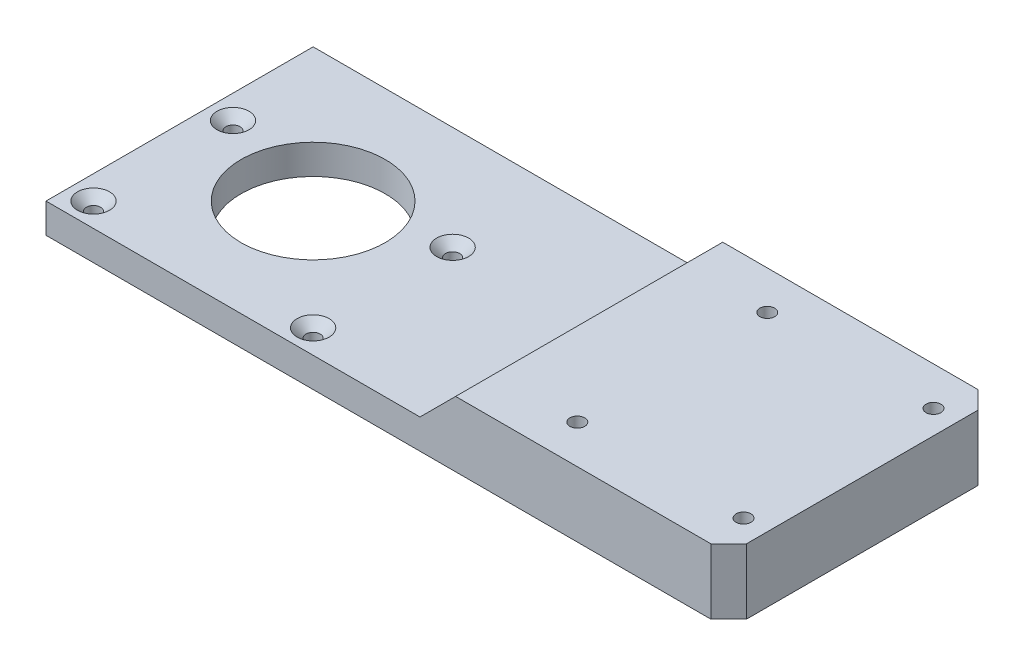
SolidWorks part; units mm, degrees
material "7075-T6, Plate (SS)"
ref_plane "Front Plane" through (0, 0, 0) normal (0, 0, 1) x (1, 0, 0)
ref_plane "Top Plane" through (0, 0, 0) normal (0, 1, 0) x (1, 0, 0)
ref_plane "Right Plane" through (0, 0, 0) normal (1, 0, 0) x (0, 0, -1)
sketch "Sketch1" plane through (0, 0, 0) normal (0, 1, 0) x (1, 0, 0)
  line L1 (0, -22.5) -> (115, -22.5)
  line L2 (0, -22.5) -> (0, 22.5)
  line L3 (0, 22.5) -> (115, 22.5)
  line L4 (115, -22.5) -> (115, 22.5)
  dimension "D1" = 45
  dimension "D2" = 115
extrude "Boss-Extrude1" add sketch "Sketch1" along normal blind 5 contours L2 L3 L4 L1
sketch "Sketch2" plane through (0, 5, 0) normal (0, 1, 0) x (1, 0, 0)
  line L0 (0, -22.5) -> (0, 22.5) construction
  circle A0 centre (22.5, 0) radius 12.142
  dimension "D2" = 24.284
  dimension "D1" = 22.5
extrude "Cut-Extrude1" cut sketch "Sketch2" against normal up to next
cosmetic thread "Cosmetic Thread1" parameters "D2"=25
hole_wizard "CSK for M2 Countersunk Flat Head Screw1" positions "Sketch3" profile "Sketch4" countersink size "M2" standard "DIN" end condition through all
sketch "Sketch3" plane through (0, 5, 0) normal (0, 1, 0) x (1, 0, 0)
  line L2 (0, -22.5) -> (115, -22.5) construction
  point P6 (4, -18.5)
  point P48 (41, -18.5)
  point P50 (41, 5)
  point P52 (4, 5)
  dimension "D3" = 4
  dimension "D5" = 37
  dimension "D6" = 27.5
sketch "Sketch4" plane through (4, 5, 18.5) normal (1, 0, 0) x (0, 0, 1)
  line L0 (0, 0) -> (0, 5)
  line L1 (0, 5) -> (1.2, 5)
  line L2 (1.2, 5) -> (1.2, 1.5)
  line L3 (1.2, 1.5) -> (2.7, 0)
  line L5 (2.7, 0) -> (0, 0)
  line L6 (-1.2, 1.5) -> (-2.7, 0) construction
  line L11 (0, -6.35) -> (0, 107.95) construction
  dimension "Thru Hole Dia." = 2.4
  dimension "Thru Hole Depth" = 5
  dimension "Near C'Sink Dia." = 5.4
  dimension "Near C'Sink Angle" = 90
sketch "Sketch13" plane through (0, 5, 0) normal (0, 1, 0) x (1, 0, 0)
  line L0 (0, -22.5) -> (115, -22.5) construction
  line L1 (115, 22.5) -> (63, 22.5)
  line L2 (115, 22.5) -> (115, -22.5)
  line L3 (115, -22.5) -> (63, -22.5)
  line L4 (63, 22.5) -> (63, -22.5)
  dimension "D1" = 52
extrude "Boss-Extrude4" add sketch "Sketch13" along normal blind 6
chamfer "Chamfer2" distance 6 angle 45 1 edges at (63, 11, 0)
hole_wizard "M3 Tapped Hole1" positions "Sketch5" profile "Sketch6" tap size "M3" standard "DIN" end condition through all
sketch "Sketch5" plane through (0, 11, 0) normal (0, 1, 0) x (1, 0, 0)
  line L1 (83, 16) -> (111, 16) construction
  line L2 (83, 16) -> (83, -16) construction
  line L3 (83, -16) -> (111, -16) construction
  line L4 (111, 16) -> (111, -16) construction
  circle A0 centre (22.5, 0) radius 12.142 construction
  point P0 (83, 16)
  point P2 (111, 16)
  point P4 (83, -16)
  point P6 (111, -16)
  point P74 (83, 0)
  point P76 (97, 16)
  dimension "D1" = 74.5
  dimension "D2" = 28
  dimension "D3" = 32
sketch "Sketch6" plane through (83, 11, -16) normal (1, 0, 0) x (0, 0, 1)
  line L0 (0, 0) -> (0, 11)
  line L1 (0, 11) -> (1.25, 11)
  line L2 (1.25, 11) -> (1.25, 0)
  line L5 (1.25, 0) -> (0, 0)
  line L11 (0, -6.35) -> (0, 107.95) construction
  dimension "Thru Tap Drill Dia." = 2.5
  dimension "Thru Tap Drill Depth" = 11
cosmetic thread "Hole Thread7" parameters "D2"=3
cosmetic thread "Hole Thread8" parameters "D2"=3
cosmetic thread "Hole Thread9" parameters "D2"=3
cosmetic thread "Hole Thread10" parameters "D2"=3
chamfer "Chamfer1" distance 3 angle 45 2 edges at (115, 5.5, -22.5) (115, 5.5, 22.5)
